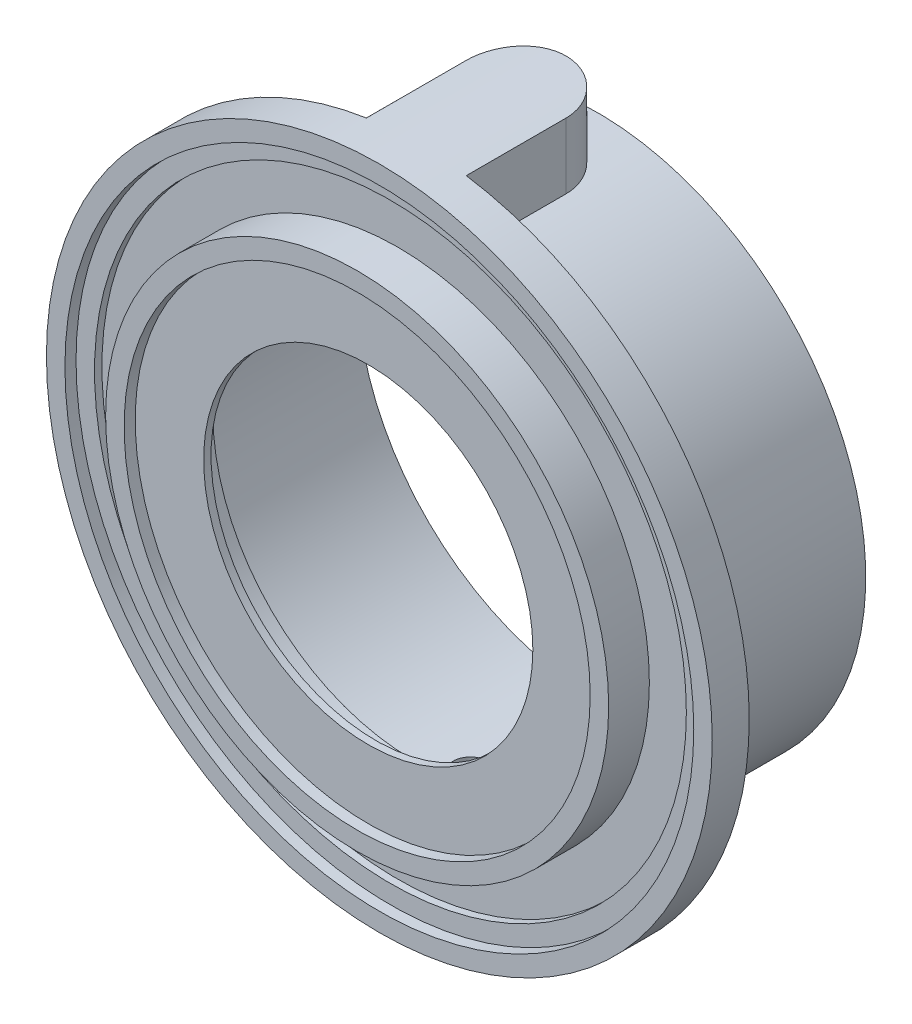
SolidWorks part; units mm, degrees
material "Acrylic (Medium-high impact)"
ref_plane "Front Plane" through (0, 0, 0) normal (0, 0, 1) x (1, 0, 0)
ref_plane "Top Plane" through (0, 0, 0) normal (0, 1, 0) x (1, 0, 0)
ref_plane "Right Plane" through (0, 0, 0) normal (1, 0, 0) x (0, 0, -1)
sketch "Sketch1" plane through (0, 0, 0) normal (0, 0, 1) x (1, 0, 0)
  circle A0 centre (0, 0) radius 4.45
  circle A1 centre (0, 0) radius 9
  dimension "D1" = 8.9
  dimension "D2" = 18
extrude "Boss-Extrude1" add sketch "Sketch1" against normal blind 6.5
sketch "Sketch2" plane through (0, 0, -6.5) normal (0, 0, -1) x (-1, 0, 0)
  circle A0 centre (0, 0) radius 7.25
  circle A1 centre (0, 0) radius 9 construction
  circle A2 centre (0, 0) radius 9
  dimension "D1" = 14.5
extrude "Cut-Extrude1" cut sketch "Sketch2" against normal blind 4.9
sketch "Sketch4" plane through (0, 0, 0) normal (0, 0, 1) x (1, 0, 0)
  circle A0 centre (0, 0) radius 6.8
  circle A1 centre (0, 0) radius 6.3
  circle M1 centre (0, 0) radius 4.45
  dimension "D1" = 13.6
  dimension "D2" = 12.6
  dimension "D3" = 0.5
extrude "Cut-Extrude2" cut sketch "Sketch4" against normal blind 0.3 contours A1 M1 region at (-6.1218, 0, 0)
sketch "Sketch5" plane through (0, 0, 0) normal (0, 0, 1) x (1, 0, 0)
  circle A1 centre (0, 0) radius 6.8 construction
  circle A3 centre (0, 0) radius 6.8
  circle M2 centre (0, 0) radius 9
extrude "Cut-Extrude3" cut sketch "Sketch5" against normal blind 0.6 contours A3 M2 region at (-8.7454, 0, 0)
sketch "Sketch6" plane through (0, 0, -0.6) normal (0, 0, 1) x (1, 0, 0)
  circle A0 centre (0, 0) radius 8.5
  circle A2 centre (0, 0) radius 9 construction
  circle A3 centre (0, 0) radius 6.8 construction
  circle M1 centre (0, 0) radius 6.8
  dimension "D1" = 0.5
  dimension "D2" = 1.7
extrude "Cut-Extrude4" cut sketch "Sketch6" against normal blind 0.3 contours A0 M1 region at (-8.2596, 0, -0.6)
sketch "Sketch7" plane through (0, 0, -6.5) normal (0, 0, -1) x (-1, 0, 0)
  circle A0 centre (0, 0) radius 6.5
  dimension "D1" = 13
extrude "Cut-Extrude5" cut sketch "Sketch7" against normal blind 5
sketch "Sketch8" plane through (0, 0, -1.5) normal (0, 0, -1) x (-1, 0, 0)
  circle A0 centre (0, 0) radius 5.4
  dimension "D1" = 10.8
extrude "Cut-Extrude6" cut sketch "Sketch8" against normal offset from surface (1 mm away) 0.2 up to face at (4.45, 0, -0.3)
ref_plane "Plane1" through (0, 7.25, 0) normal (0, 1, 0) x (1, 0, 0)
sketch "Sketch9" plane through (0, 7.25, 0) normal (0, 1, 0) x (1, 0, 0)
  line L0 (0, 0) -> (0, 6.5) construction
  line L1 (6.5, 6.5) -> (-6.5, 6.5) construction
  line L2 (-1.35, 1.6) -> (-1.35, 4.3)
  line L3 (9, 1.6) -> (-9, 1.6) construction
  line L4 (1.35, 1.6) -> (1.35, 4.3)
  line L5 (-1.35, 1.6) -> (1.35, 1.6)
  line L6 (-9, 0.6) -> (9, 0.6) construction
  arc A0 (-1.35, 4.3) -> (1.35, 4.3) centre (0, 4.3) cw
  dimension "D1" = 2.7
  dimension "D2" = 5.05
extrude "Boss-Extrude5" add sketch "Sketch9" along normal up to surface and the other way up to surface separate body contours L4 A0 L2 L5 up to face at (-9, 0, -1.6) other way up to face at (-7.25, 0, -1.6)
mirror "Mirror2" about plane through (0, 0, 0) normal (0, 1, 0) of bodies 111
combine bodies "Combine3" operation type add bodies to combine 111 107 112
sketch "Sketch11" plane through (0, 0, 0) normal (0, 1, 0) x (1, 0, 0)
  line L0 (-9, 0.6) -> (9, 0.6) construction
  circle A0 centre (0, 3.1) radius 0.5
  dimension "D1" = 1
  dimension "D2" = 2
  dimension "D3" = 2.5
extrude "Cut-Extrude7" cut sketch "Sketch11" against normal through all
sketch "Sketch12" plane through (0, 0, -0.9) normal (0, 0, 1) x (1, 0, 0)
  circle A0 centre (0, 0) radius 8
  circle A1 centre (0, 0) radius 8.5 construction
  circle M1 centre (0, 0) radius 6.8
  dimension "D1" = 0.5
extrude "Cut-Extrude8" cut sketch "Sketch12" against normal blind 0.2 contours A0 M1 region at (-7.7737, 0, -0.9)
